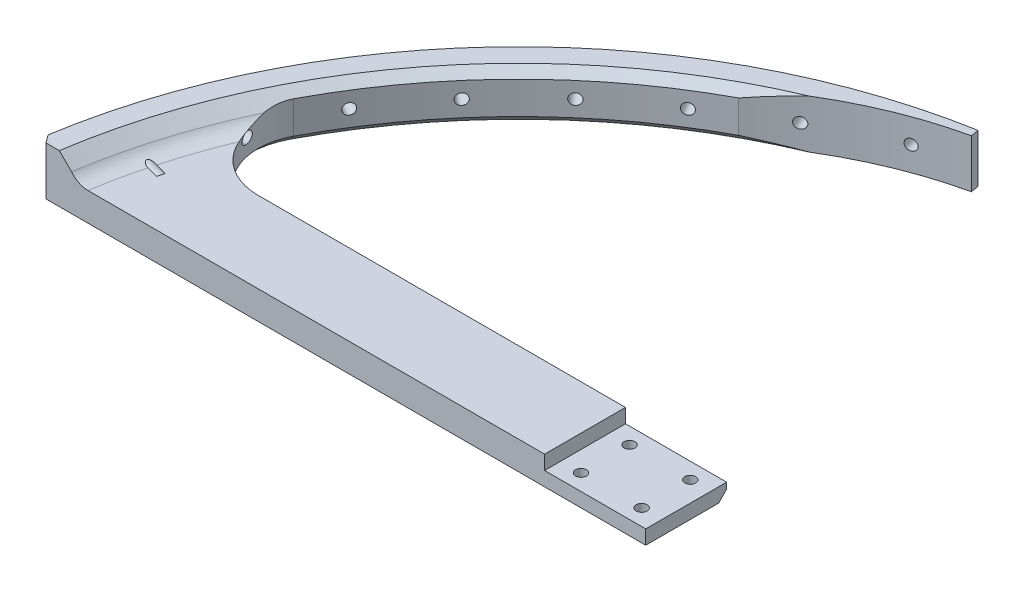
SolidWorks part; units mm, degrees
ref_plane "Front Plane" through (0, 0, 0) normal (0, 0, 1) x (1, 0, 0)
ref_plane "Top Plane" through (0, 0, 0) normal (0, 1, 0) x (1, 0, 0)
ref_plane "Right Plane" through (0, 0, 0) normal (1, 0, 0) x (0, 0, -1)
sketch "Sketch1" plane through (0, 0, 0) normal (0, 1, 0) x (1, 0, 0)
  line L0 (0, 0) -> (-24.3107, 137.8731) construction
  line L1 (0, 0) -> (-140, 0) construction
  line L2 (0, 0) -> (-138.5641, 20) construction
  line L3 (-138.5641, 20) -> (-138.5641, 0) construction
  line L4 (-24.3107, 137.8731) -> (-23.0952, 130.9794)
  line L5 (-138.5641, 20) -> (11.4359, 20)
  line L6 (11.4359, 20) -> (11.4359, 40)
  line L7 (11.4359, 40) -> (-126.8424, 40)
  circle A0 centre (0, 0) radius 140 construction
  circle A1 centre (0, 0) radius 140 construction
  arc A2 (-131.6359, 19) -> (-126.8424, 40) centre (0, 0) ccw construction
  arc A3 (-138.5641, 20) -> (-24.3107, 137.8731) centre (0, 0) cw
  arc A5 (-126.8424, 40) -> (-23.0952, 130.9794) centre (0, 0) cw
  circle A7 centre (0, 0) radius 133 construction
  dimension "D1" = 280
  dimension "D4" = 20
  dimension "D5" = 80
  dimension "D7" = 20
  dimension "D8" = 150
  dimension "D2" = 0
  dimension "D3" = 7
extrude "Boss-Extrude1" add sketch "Sketch1" along normal blind 7 contours L7 A5 L4 A3 L5 L6 region at (-25.5817, 0, -134.095)
sketch "Sketch2" plane through (0, 7, 0) normal (0, 1, 0) x (1, 0, 0)
  line L0 (-24.3107, 137.8731) -> (-23.0952, 130.9794) construction
  line L5 (-138.5641, 20) -> (-131.4876, 20)
  line L6 (-138.5641, 20) -> (11.4359, 20) construction
  line L7 (-24.3107, 137.8731) -> (-23.0952, 130.9794)
  arc A0 (-138.5641, 20) -> (-24.3107, 137.8731) centre (0, 0) cw
  arc A1 (-138.5641, 20) -> (-24.3107, 137.8731) centre (0, 0) cw
  arc A4 (-131.4876, 20) -> (-23.0952, 130.9794) centre (0, 0) cw
  arc A5 (-131.6359, 19) -> (-23.0952, 130.9794) centre (0, 0) cw construction
  arc M2 (-126.8424, 40) -> (-23.0952, 130.9794) centre (0, 0) cw
  line M3 (-23.0952, 130.9794) -> (-24.3107, 137.8731)
  arc M4 (-24.3107, 137.8731) -> (-138.5641, 20) centre (0, 0) ccw
  line M5 (-138.5641, 20) -> (11.4359, 20)
  dimension "D1" = 0
  dimension "D2" = 7
extrude "Boss-Extrude2" add sketch "Sketch2" along normal blind 5 contours A4 M5 M2 M3 M4 region at (-99.3416, 7, -96.2909)
fillet "Fillet1" radius 15 1 edges at (-126.8424, 3.5, -40)
sketch "Sketch3" plane through (0, 12, 0) normal (0, 1, 0) x (1, 0, 0)
  line L1 (-23.0952, 130.9794) -> (-23.9634, 135.9035)
  arc A0 (-23.0952, 130.9794) -> (-131.4876, 20) centre (0, 0) ccw construction
  arc A1 (-62.8388, 117.219) -> (-23.0952, 130.9794) centre (0, 0) cw
  spline S0 degree 2 poles (-62.8388, 117.219) (-44.9026, 131.2279) (-23.9634, 135.9035) knots 0 0 0 0.833738 0.833738 0.833738
  dimension "D1" = 5
extrude "Cut-Extrude1" cut sketch "Sketch3" against normal up to surface (12 mm away) up to face at (-59.78, 0, -68.0808)
fillet "Fillet2" radius 5 1 edges at (-126.3353, 7, -41.5739)
sketch "Sketch4" plane through (0, 7, 0) normal (0, 1, 0) x (1, 0, 0)
  line L0 (-126.4278, 20) -> (11.4359, 20) construction
  line L1 (11.4359, 40) -> (-13.5641, 40)
  line L2 (11.4359, 40) -> (11.4359, 20)
  line L3 (11.4359, 20) -> (-13.5641, 20)
  line L4 (-13.5641, 40) -> (-13.5641, 20)
  dimension "D1" = 25
extrude "Cut-Extrude2" cut sketch "Sketch4" against normal blind 3.5
sketch "Sketch6" plane through (0, 3.5, 0) normal (0, 1, 0) x (1, 0, 0)
  line L0 (-13.5641, 30) -> (11.4359, 30) construction
  line L1 (-13.5641, 40) -> (-13.5641, 20) construction
  line L2 (11.4359, 20) -> (11.4359, 40) construction
  line L4 (-8.5641, 24) -> (6.4359, 24) construction
  line L5 (-8.5641, 24) -> (-8.5641, 36) construction
  line L6 (-8.5641, 36) -> (6.4359, 36) construction
  line L7 (6.4359, 24) -> (6.4359, 36) construction
  line L8 (-8.5641, 24) -> (6.4359, 36) construction
  line L9 (-8.5641, 36) -> (6.4359, 24) construction
  circle A0 centre (-8.5641, 36) radius 1.35
  circle A1 centre (6.4359, 36) radius 1.35
  circle A2 centre (-8.5641, 24) radius 1.35
  circle A3 centre (6.4359, 24) radius 1.35
  point P6 (-1.0641, 30)
  dimension "D1" = 15
  dimension "D2" = 12
extrude "Cut-Extrude3" cut sketch "Sketch6" against normal up to surface (3.5 mm away) up to face at (-62.2171, 0, -72.8127)
sketch "Sketch7" plane through (0, 0, 0) normal (1, 0, 0) x (0, 0, -1)
  line L0 (0, 0) -> (0, 6) construction
  line L1 (0, 6) -> (137.8731, 6) construction
  line L2 (137.8731, 12) -> (137.8731, 0) construction
  dimension "D1" = 6
ref_plane "Plane1" through (0, 6, -137.8731) normal (0, 0, -1) x (-1, 0, 0)
sketch "Sketch8" plane through (0, 6, -137.8731) normal (0, 0, -1) x (-1, 0, 0)
  line L0 (0, -6) -> (0, 0) construction
  circle A0 centre (0, 0) radius 1.35
  dimension "D1" = 2.7
ref_plane "Plane2" through (0, 6, 0) normal (0, 1, 0) x (1, 0, 0)
sketch "Sketch9" plane through (0, 6, 0) normal (0, 1, 0) x (1, 0, 0)
  line L0 (0, 0) -> (-135.2296, 36.2347) construction
  line L1 (-126.4278, 20) -> (-13.5641, 20) construction
  arc A0 (-24.3107, 137.8731) -> (-138.5641, 20) centre (0, 0) ccw construction
  dimension "D1" = 15
ref_plane "Plane3" through (-135.2296, 6, -36.2347) normal (-0.9659, 0, -0.2588) x (-0.2588, 0, 0.9659)
sketch "Sketch10" plane through (-135.2296, 6, -36.2347) normal (-0.9659, 0, -0.2588) x (-0.2588, 0, 0.9659)
  circle A0 centre (0, 0) radius 1.35
extrude "Cut-Extrude5" cut sketch "Sketch10" against normal blind 15
pattern_circular "CirPattern1" count 8 over 60 about axis through (0, 0, 0) along (0, 1, 0) of "Cut-Extrude5" reverse direction yes
chamfer "Chamfer1" distance 2 angle 45 1 edges at (-138.5641, 6, -20) first distance on face at (-128.3187, 6, -55.9849)
chamfer "Chamfer2" distance 2 angle 45 4 edges at (-94.3838, 12, -93.7054) (-46.4812, 0, -40) (-117.241, 0, -47.2499) (-94.3838, 0, -93.7054)
